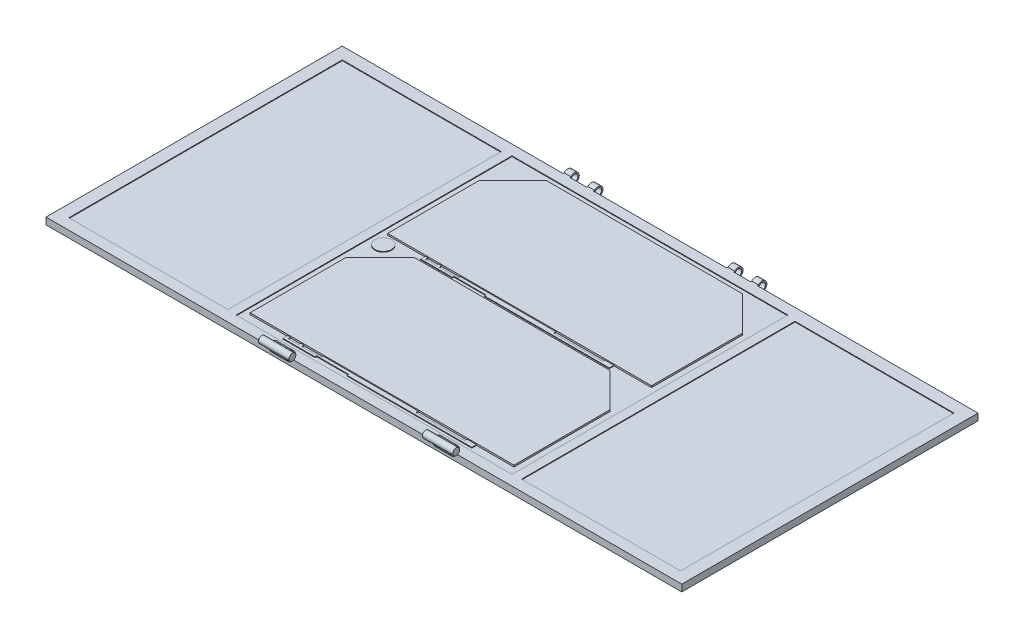
SolidWorks part; units mm, degrees
ref_plane "Front Plane" through (0, 0, 0) normal (0, 0, 1) x (1, 0, 0)
ref_plane "Top Plane" through (0, 0, 0) normal (0, 1, 0) x (1, 0, 0)
ref_plane "Right Plane" through (0, 0, 0) normal (1, 0, 0) x (0, 0, -1)
sketch "Sketch1" plane through (0, 0, 0) normal (0, 1, 0) x (1, 0, 0)
  line L1 (43.6214, -43.6214) -> (-43.6214, -43.6214)
  line L2 (43.6214, -43.6214) -> (43.6214, 43.6214)
  line L3 (43.6214, 43.6214) -> (-43.6214, 43.6214)
  line L4 (-43.6214, -43.6214) -> (-43.6214, 43.6214)
  line L5 (43.6214, -43.6214) -> (-43.6214, 43.6214) construction
  line L6 (43.6214, 43.6214) -> (-43.6214, -43.6214) construction
  circle A0 centre (0, 0) radius 38
extrude "Boss-Extrude1" add sketch "Sketch1" along normal blind 2 contours L3 L4 L1 L2
sketch "Sketch2" plane through (-43.6214, 0, 0) normal (-1, 0, 0) x (0, 0, 1)
  circle A0 centre (-45.0302, 1.0744) radius 1.4088
extrude "Boss-Extrude2" add sketch "Sketch2" against normal blind 2 from offset 15 separate body offset against normal yes
sketch "Sketch3" plane through (-28.6214, 0, 0) normal (-1, 0, 0) x (0, 0, 1)
  circle A0 centre (-45.0302, 1.0744) radius 1
sketch "Sketch4" plane through (-28.6214, 0, 0) normal (-1, 0, 0) x (0, 0, 1)
  line L0 (-43.2204, 0) -> (-44.5765, 0)
  line L1 (43.6214, 0) -> (-43.6214, 0) construction
  line L2 (-43.2204, 2) -> (-44.6517, 2)
  line L3 (43.6214, 2) -> (-43.6214, 2) construction
  line L4 (-44.6517, 2) -> (-44.5765, 0)
  line L5 (-43.2204, 2) -> (-43.2204, 0)
  circle A0 centre (-45.0302, 1.0744) radius 1 construction
extrude "Boss-Extrude3" add sketch "Sketch4" against normal blind 2
sketch "Sketch6" plane through (-26.6214, 0, 0) normal (1, 0, 0) x (0, 0, -1)
  line L0 (43.6214, 2) -> (43.9681, 2)
  line L1 (43.6214, 2) -> (43.9681, 2) construction
  line L2 (43.6214, 0) -> (43.6214, 2) construction
  line L3 (43.6214, 2) -> (43.6214, 0)
  line L4 (43.6214, 0) -> (44.119, 0)
  arc A0 (44.119, 0) -> (43.9681, 2) centre (45.0302, 1.0744) ccw
extrude "Boss-Extrude4" add sketch "Sketch6" along normal blind 2 from offset 5
sketch "Sketch8" plane through (43.6214, 0, 0) normal (1, 0, 0) x (0, 0, -1)
  line L0 (43.9681, 2) -> (43.6214, 2)
  line L1 (43.6214, 2) -> (43.6214, 0)
  line L2 (43.6214, 0) -> (44.119, 0)
  arc A0 (44.119, 0) -> (43.9681, 2) centre (45.0302, 1.0744) ccw
extrude "Boss-Extrude5" add sketch "Sketch8" against normal blind 2 from offset 15 offset against normal yes
sketch "Sketch9" plane through (26.6214, 0, 0) normal (-1, 0, 0) x (0, 0, 1)
  line L0 (-43.9681, 2) -> (-43.6214, 2)
  line L1 (-43.6214, 2) -> (-43.6214, 0)
  line L2 (-44.119, 0) -> (-43.6214, 0) construction
  line L3 (-43.6214, 0) -> (-43.6214, 2) construction
  line L4 (-43.6214, 0) -> (-44.119, 0)
  arc A0 (-43.9681, 2) -> (-44.119, 0) centre (-45.0302, 1.0744) ccw
extrude "Boss-Extrude6" add sketch "Sketch9" along normal blind 2 from offset 5
extrude "Cut-Extrude1" cut sketch "Sketch3" against normal blind 92 contours A0
sketch "Sketch10" plane through (0, 2, 0) normal (0, 1, 0) x (1, 0, 0)
  line L54 (40.6214, 40.6214) -> (-40.6214, 40.6214)
  line L55 (40.6214, 40.6214) -> (-40.6214, 40.6214)
  line L60 (-40.6214, 40.6214) -> (-40.6214, -40.6214)
  line L61 (-40.6214, -40.6214) -> (40.6214, -40.6214)
  line L62 (40.6214, -40.6214) -> (40.6214, 40.6214)
  line L64 (-40.6214, 40.6214) -> (-40.6214, -40.6214)
  line L65 (-40.6214, -40.6214) -> (40.6214, -40.6214)
  line L66 (40.6214, -40.6214) -> (40.6214, 40.6214)
  dimension "D1" = 3
extrude "Cut-Extrude2" cut sketch "Sketch10" against normal blind 0.2
sketch "Sketch11" plane through (0, 1.8, 0) normal (0, 1, 0) x (1, 0, 0)
  line L1 (38.8561, 39.0792) -> (-38.8561, 39.0792)
  line L2 (38.8561, 39.0792) -> (38.8561, 2.2297)
  line L3 (38.8561, 2.2297) -> (-38.8561, 2.2297)
  line L4 (-38.8561, 39.0792) -> (-38.8561, 2.2297)
  line L5 (38.8561, 39.0792) -> (-38.8561, 2.2297) construction
  line L6 (38.8561, 2.2297) -> (-38.8561, 39.0792) construction
  line L7 (38.8561, -38.2682) -> (-38.8561, -38.2682)
  line L8 (38.8561, -38.2682) -> (38.8561, 0)
  line L9 (38.8561, 0) -> (-38.8561, 0)
  line L10 (-38.8561, -38.2682) -> (-38.8561, 0)
  line L11 (38.8561, -38.2682) -> (-38.8561, 0) construction
  line L12 (38.8561, 0) -> (-38.8561, -38.2682) construction
  point P0 (0, 20.6544)
  point P5 (0, -19.1341)
extrude "Boss-Extrude7" add sketch "Sketch11" along normal blind 0.5
chamfer "Chamfer1" distance 10 angle 45 4 edges at (38.8561, 2.05, 0) (-38.8561, 2.05, 0) (38.8561, 2.05, -39.0792) (-38.8561, 2.05, -39.0792)
sketch "Sketch12" plane through (0, 1.8, 0) normal (0, 1, 0) x (1, 0, 0)
  line L0 (-38.8561, 2.2297) -> (38.8561, 2.2297) construction
  line L1 (27.8133, 0.8453) -> (-8.9831, 0.8453)
  line L2 (27.8133, 0.8453) -> (27.8133, 2.2297)
  line L3 (27.8133, 2.2297) -> (25.1091, 2.2297)
  line L4 (-27.8133, 0.8453) -> (-27.8133, 2.2297)
  line L6 (27.8133, 2.2297) -> (25.1091, 2.1624) construction
  line L7 (10.7335, 2.2297) -> (-17.4042, 2.2297)
  line L9 (-26.9367, 2.2297) -> (-26.9367, 1.5375)
  line L10 (-26.9367, 1.5375) -> (-23.843, 1.5375)
  line L11 (-23.843, 2.2297) -> (-23.843, 1.5375)
  line L15 (-22.9642, 2.2297) -> (-22.9642, 1.5375)
  line L16 (-22.9642, 1.5375) -> (-17.4042, 1.5375)
  line L17 (-17.4042, 2.2297) -> (-17.4042, 1.5375)
  line L18 (-26.9367, 2.2297) -> (-27.8133, 2.2297)
  line L19 (-26.9367, 2.2079) -> (-27.8133, 2.2297) construction
  line L20 (-18.3781, 0.8453) -> (-27.8133, 0.8453)
  line L21 (-18.3781, 0.8453) -> (-18.3781, 1.314)
  line L22 (-18.3781, 1.314) -> (-8.9831, 1.314)
  line L23 (-8.9831, 0.8453) -> (-8.9831, 1.314)
  line L27 (10.7335, 2.2297) -> (10.7335, 1.5375)
  line L28 (10.7335, 1.5375) -> (25.1091, 1.5375)
  line L29 (25.1091, 2.2297) -> (25.1091, 1.5375)
  line L30 (-22.9642, 2.2297) -> (-23.843, 2.2297)
  line L32 (-22.9642, 2.109) -> (-23.843, 2.1309) construction
  point P0 (0, 1.5375)
  point P7 (-25.3899, 3.6579)
  point P12 (-20.1842, 3.6579)
  point P17 (-13.6806, -0.4859)
  point P22 (17.9213, 5.7783)
extrude "Boss-Extrude8" add sketch "Sketch12" along normal blind 0.2
pattern_linear "LPattern2" count 2 spacing 40.5 along (0, 0, 1) of "Boss-Extrude8"
sketch "Sketch13" plane through (0, 1.8, 0) normal (0, 1, 0) x (1, 0, 0)
  circle A0 centre (-36.9385, -0.9703) radius 2.4757
extrude "Boss-Extrude9" add sketch "Sketch13" along normal blind 0.2
ref_plane "Plane1" through (0, 1, 0) normal (0, 1, 0) x (1, 0, 0)
mirror "Mirror3" about plane through (0, 1, 0) normal (0, 1, 0) of "Cut-Extrude2"
mirror "Mirror4" about plane through (0, 1, 0) normal (0, 1, 0) of "Boss-Extrude9", "Boss-Extrude7", "LPattern2"
chamfer "Chamfer2" distance 10 angle 45 4 edges at (38.8561, -0.05, -39.0792) (-38.8561, -0.05, -39.0792) (-38.8561, -0.15, 0) (38.8561, -0.05, 0)
sketch "Sketch15" plane through (43.6214, 0, 0) normal (1, 0, 0) x (0, 0, -1)
  line L0 (-43.6214, 1) -> (-45.0314, 1) construction
  line L1 (-43.6214, 2) -> (-43.6214, 0) construction
  line L2 (-45.0314, 1) -> (-45.0314, 4) construction
  circle A0 centre (-45.0314, 4) radius 1
extrude "Boss-Extrude10" add sketch "Sketch15" against normal blind 9 from offset 15 separate body offset against normal yes
sketch "Sketch16" plane through (0, 2, 0) normal (0, 1, 0) x (1, 0, 0)
  line L0 (26.6214, 46.439) -> (26.6214, -49.7129) construction
  line L1 (21.6214, 46.439) -> (21.6214, -49.7129) construction
  line L2 (-26.6214, 46.0302) -> (-26.6214, -47.0906) construction
  line L3 (-26.6214, 44.0302) -> (-26.6214, 46.0302) construction
  line L4 (-26.6214, 43.9681) -> (-26.6214, 46.439) construction
  line L5 (-21.6214, 46.439) -> (-21.6214, -49.7129) construction
sketch "Sketch17" plane through (-43.6214, 0, 0) normal (-1, 0, 0) x (0, 0, 1)
  circle A0 centre (45.0314, 4) radius 1
extrude "Boss-Extrude11" add sketch "Sketch17" against normal blind 9 from offset 15 separate body offset against normal yes
sketch "Sketch18" plane through (0, 2, 0) normal (0, 1, 0) x (1, 0, 0)
  line L0 (-21.6214, 46.439) -> (-21.6214, -49.7129) construction
  line L1 (21.6214, 46.439) -> (21.6214, -49.7129) construction
  line L2 (-26.6214, -42.054) -> (-26.6214, -44.8269)
  line L3 (-26.6214, -44.8269) -> (-21.6214, -44.8269)
  line L4 (-21.6214, -42.054) -> (-21.6214, -44.8269)
  line L5 (-24.1214, -42.054) -> (-21.6214, -44.8269) construction
  line L6 (-26.6214, -44.8269) -> (-24.1214, -42.054) construction
  line L7 (-26.6214, -42.054) -> (-21.6214, -42.054)
  line L8 (21.6214, -42.054) -> (26.6214, -42.054)
  line L9 (21.6214, -42.054) -> (21.6214, -44.8269)
  line L10 (21.6214, -44.8269) -> (26.6214, -44.8269)
  line L11 (26.6214, -42.054) -> (26.6214, -44.8269)
  line L12 (26.6214, 46.439) -> (26.6214, -49.7129) construction
  point P0 (-24.1214, -42.054)
extrude "Boss-Extrude12" add sketch "Sketch18" along normal blind 2 and the other way blind 1
fillet "Fillet1" radius 2 4 edges at (-24.1214, 4, 42.054) (24.1214, 4, 42.054) (24.1214, 1, 44.8269) (-24.1214, 1, 44.8269)
sketch "Sketch19" plane through (43.6214, 0, 0) normal (1, 0, 0) x (0, 0, -1)
  line L0 (-43.6214, 2) -> (43.6214, 2)
  line L1 (43.6214, 2) -> (43.6214, 0)
  line L2 (43.6214, 0) -> (-43.6214, 0)
  line L3 (-43.6214, 0) -> (-43.6214, 2)
extrude "Boss-Extrude13" add sketch "Sketch19" along normal blind 50
sketch "Sketch20" plane through (-43.6214, 0, 0) normal (-1, 0, 0) x (0, 0, 1)
  line L0 (43.6214, 2) -> (43.6214, 0)
  line L1 (43.6214, 0) -> (-43.6214, 0)
  line L2 (-43.6214, 0) -> (-43.6214, 2)
  line L3 (-43.6214, 2) -> (43.6214, 2)
extrude "Boss-Extrude14" add sketch "Sketch20" along normal blind 50
sketch "Sketch24" plane through (0, 2, 0) normal (0, 1, 0) x (1, 0, 0)
  line L0 (-43.258, 40.0921) -> (-90.0716, 40.0921)
  line L1 (-90.0716, 40.0921) -> (-90.0716, -40.4272)
  line L2 (-90.0716, -40.4272) -> (-43.258, -40.4272)
  line L3 (-43.258, -40.4272) -> (-43.258, 40.0921)
  line L5 (0, 60.9152) -> (0, -67.336) construction
  line L6 (90.0716, -40.4272) -> (43.258, -40.4272)
  line L7 (90.0716, 40.0921) -> (90.0716, -40.4272)
  line L8 (43.258, 40.0921) -> (90.0716, 40.0921)
  line L9 (43.258, -40.4272) -> (43.258, 40.0921)
extrude "Cut-Extrude3" cut sketch "Sketch24" against normal blind 0.2
sketch "Sketch29" plane through (0, 0, 0) normal (0, -1, 0) x (-1, 0, 0)
  line L5 (43.0578, -40.3259) -> (90.193, -40.3259)
  line L6 (90.193, -40.3259) -> (90.193, 41.3859)
  line L7 (90.193, 41.3859) -> (43.0578, 41.3859)
  line L8 (43.0578, 41.3859) -> (43.0578, -40.3259)
  line L9 (0, -60.2238) -> (0, 62.5886) construction
  line L10 (-90.193, 41.3859) -> (-43.0578, 41.3859)
  line L11 (-90.193, -40.3259) -> (-90.193, 41.3859)
  line L12 (-43.0578, -40.3259) -> (-90.193, -40.3259)
  line L13 (-43.0578, 41.3859) -> (-43.0578, -40.3259)
extrude "Cut-Extrude5" cut sketch "Sketch29" against normal blind 0.2
equation "\"z\"=10"
equation "\"2.00mmz\"=2"
